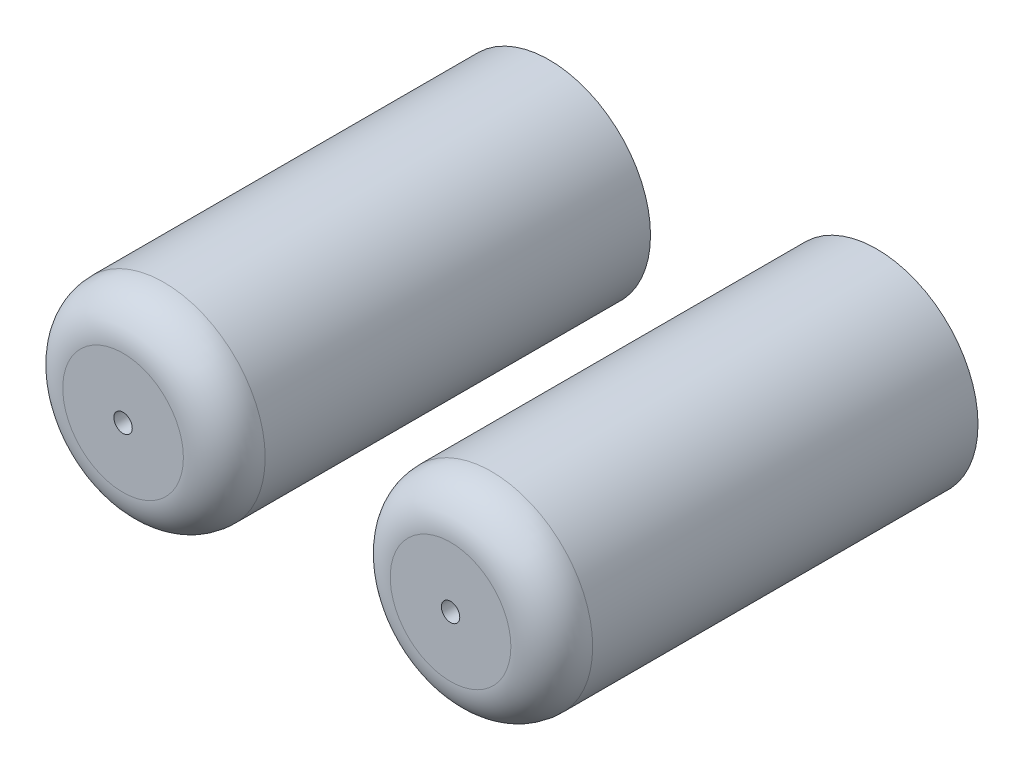
SolidWorks part; units mm, degrees
material "Plastique personnalisé"
ref_plane "Plan de face" through (0, 0, 0) normal (0, 0, 1) x (1, 0, 0)
ref_plane "Plan de dessus" through (0, 0, 0) normal (0, 1, 0) x (1, 0, 0)
ref_plane "Plan de droite" through (0, 0, 0) normal (1, 0, 0) x (0, 0, -1)
sketch "Esquisse1" plane through (0, 0, 0) normal (0, 0, 1) x (1, 0, 0)
  line L0 (0, 0) -> (40.04, 0) construction
  circle A0 centre (0, 0) radius 12.375
  circle A1 centre (40.04, 0) radius 12.375
  dimension "D1" = 40.04
  dimension "D2" = 24.75
  dimension "D3" = 24.75
extrude "Boss.-Extru.1" add sketch "Esquisse1" along normal blind 52.11
fillet "Congé1" radius 5 1 edges at (52.415, 0, 52.11)
fillet "Congé2" radius 5 1 edges at (12.375, 0, 52.11)
sketch "Esquisse2" plane through (0, 0, 52.11) normal (0, 0, 1) x (1, 0, 0)
  circle A0 centre (0, 0) radius 1.125
  circle A1 centre (40.04, 0) radius 1.125
extrude "Enlèv. mat.-Extru.1" cut sketch "Esquisse2" against normal blind 52.11
sketch "Esquisse3" plane through (0, 0, 0) normal (0, 0, -1) x (-1, 0, 0)
  circle A0 centre (0, 0) radius 1.5
  circle A1 centre (-40.04, 0) radius 1.5
extrude "Enlèv. mat.-Extru.2" cut sketch "Esquisse3" against normal blind 20
fillet "Congé3" radius 0.25 1 edges at (38.54, 0, 20)
fillet "Congé4" radius 0.25 1 edges at (38.915, 0, 20)
fillet "Congé5" radius 0.25 1 edges at (-1.125, 0, 20)
fillet "Congé6" radius 0.25 1 edges at (-1.5, 0, 20)
sketch "Esquisse4" plane through (0, 0, 0) normal (0, 0, -1) x (-1, 0, 0)
  line L0 (-40.04, 0) -> (0, 0) construction
ref_axis "Axe1" through (40.04, 0, 0) along (-1, 0, 0)
